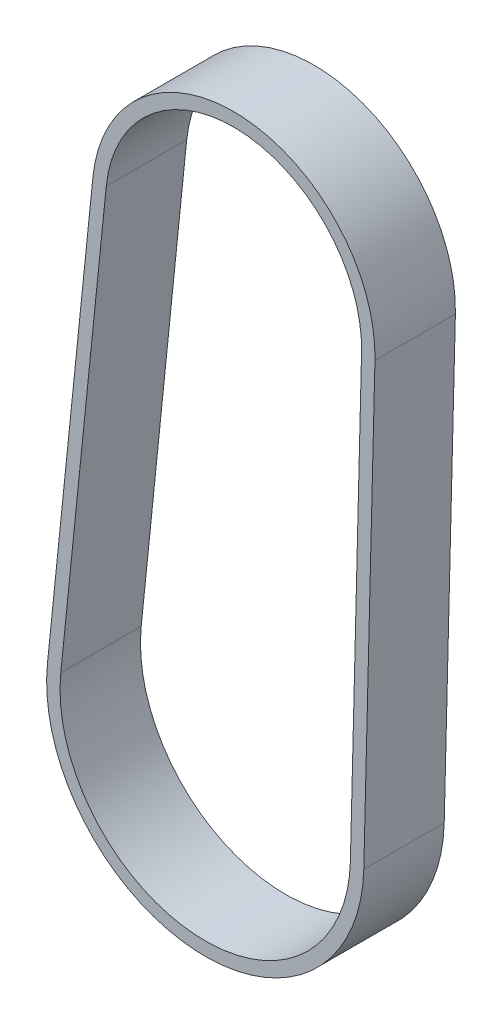
SolidWorks part; units mm, degrees
ref_plane "Front Plane" through (0, 0, 0) normal (0, 0, 1) x (1, 0, 0)
ref_plane "Top Plane" through (0, 0, 0) normal (0, 1, 0) x (1, 0, 0)
ref_plane "Right Plane" through (0, 0, 0) normal (1, 0, 0) x (0, 0, -1)
sketch "Sketch2" plane through (0, 0, 0) normal (0, 0, 1) x (1, 0, 0)
  line L0 (0, 0) -> (1, 0) construction
  line L1 (0, 0) -> (0, 1) construction
  line L4 (-19.3404, -48.2433) -> (-14.2494, 1.4596)
  line L5 (14.3195, -0.3582) -> (13.0699, -50.3055)
  arc A2 (13.0699, -50.3055) -> (-19.3404, -48.2433) centre (-3.175, -49.8991) cw
  arc A3 (-14.2494, 1.4596) -> (14.3195, -0.3582) centre (0, 0) cw
extrude "Extrude-Thin1" add sketch "Sketch2" along normal blind 9 thin thin type one direction wall 1.5
